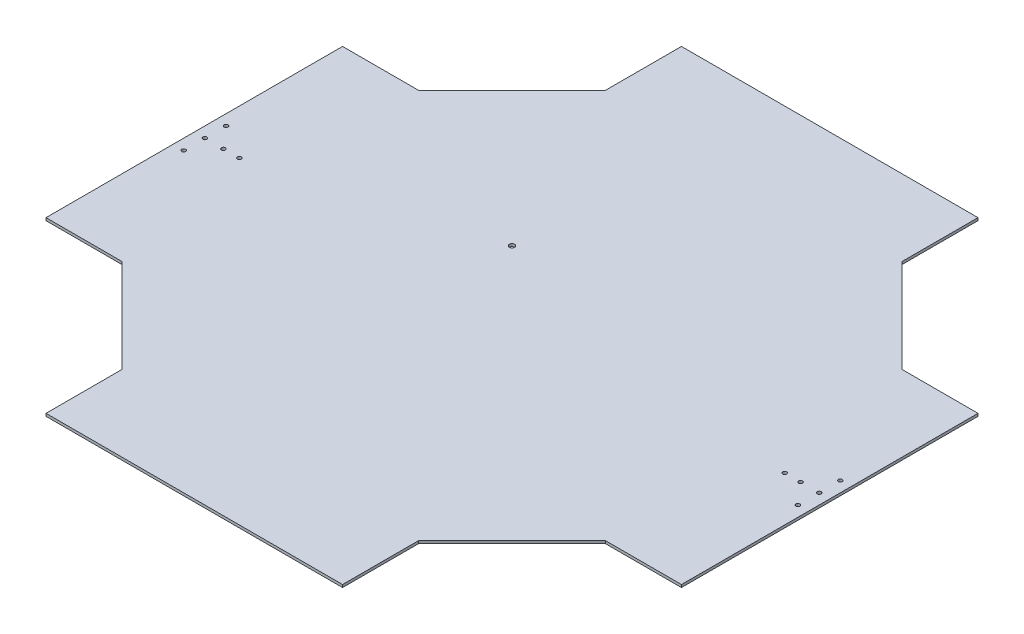
SolidWorks part; units mm, degrees
material "Acrylic (Medium-high impact)"
ref_plane "Front Plane" through (0, 0, 0) normal (0, 0, 1) x (1, 0, 0)
ref_plane "Top Plane" through (0, 0, 0) normal (0, 1, 0) x (1, 0, 0)
ref_plane "Right Plane" through (0, 0, 0) normal (1, 0, 0) x (0, 0, -1)
sketch "Sketch1" plane through (0, 0, 0) normal (0, 1, 0) x (1, 0, 0)
  line L0 (-381, 177.8) -> (-289.7187, 177.8)
  line L1 (-177.8, -381) -> (177.8, -381)
  line L2 (-381, -177.8) -> (-381, 177.8)
  line L3 (-177.8, 381) -> (177.8, 381)
  line L4 (381, -177.8) -> (381, 177.8)
  line L5 (0, 381) -> (0, -381) construction
  line L6 (-381, 0) -> (381, 0) construction
  line L7 (-289.7187, 177.8) -> (-177.8, 289.7188)
  line L8 (-177.8, 289.7188) -> (-177.8, 381)
  line L9 (177.8, 289.7188) -> (177.8, 381)
  line L10 (289.7187, 177.8) -> (177.8, 289.7188)
  line L11 (381, 177.8) -> (289.7187, 177.8)
  line L12 (-381, -177.8) -> (-289.7187, -177.8)
  line L13 (-177.8, -289.7188) -> (-177.8, -381)
  line L14 (381, -177.8) -> (289.7187, -177.8)
  line L15 (177.8, -289.7188) -> (177.8, -381)
  line L16 (289.7187, -177.8) -> (177.8, -289.7188)
  line L17 (-289.7187, -177.8) -> (-177.8, -289.7188)
  point P0 (0, 0)
  dimension "D1" = 762
  dimension "D2" = 135
  dimension "D3" = 203.2
  dimension "D4" = 91.2812
extrude "Boss-Extrude1" add sketch "Sketch1" along normal mid plane 3.175
sketch "Sketch2" plane through (0, 1.5875, 0) normal (0, 1, 0) x (1, 0, 0)
  line L0 (0, 0) -> (-50000, 0) construction
  line L1 (-368.3, -25.4) -> (-368.3, 25.4) construction
  line L2 (-381, 177.8) -> (-381, -177.8) construction
  line L3 (0, 0) -> (0, 50000) construction
  line L4 (368.3, -25.4) -> (368.3, 25.4) construction
  circle A0 centre (-346.075, 0) radius 2.3813
  circle A1 centre (-368.3, 0) radius 2.3813
  circle A2 centre (-368.3, 25.4) radius 2.3813
  circle A3 centre (-368.3, -25.4) radius 2.3813
  circle A4 centre (368.3, -25.4) radius 2.3813
  circle A5 centre (368.3, 25.4) radius 2.3813
  circle A6 centre (368.3, 0) radius 2.3813
  circle A7 centre (346.075, 0) radius 2.3813
  circle A8 centre (-327.025, 0) radius 2.3813
  circle A9 centre (327.025, 0) radius 2.3813
  point P15 (-368.3, 0)
  point P25 (368.3, 0)
  dimension "D1" = 4.7625
  dimension "D5" = 19.05
  dimension "D6" = 19.05
  dimension "D2" = 50.8
  dimension "D3" = 22.225
  dimension "D4" = 12.7
extrude "Cut-Extrude1" cut sketch "Sketch2" against normal through all
sketch "Sketch3" plane through (0, 1.5875, 0) normal (0, 1, 0) x (1, 0, 0)
  line L0 (177.8, 381) -> (-177.8, 381) construction
  line L1 (-381, 177.8) -> (-381, -177.8) construction
  circle A0 centre (-72.39, 72.39) radius 3.175
  dimension "D3" = 6.35
  dimension "D1" = 308.61
  dimension "D2" = 308.61
extrude "Cut-Extrude2" cut sketch "Sketch3" against normal through all
